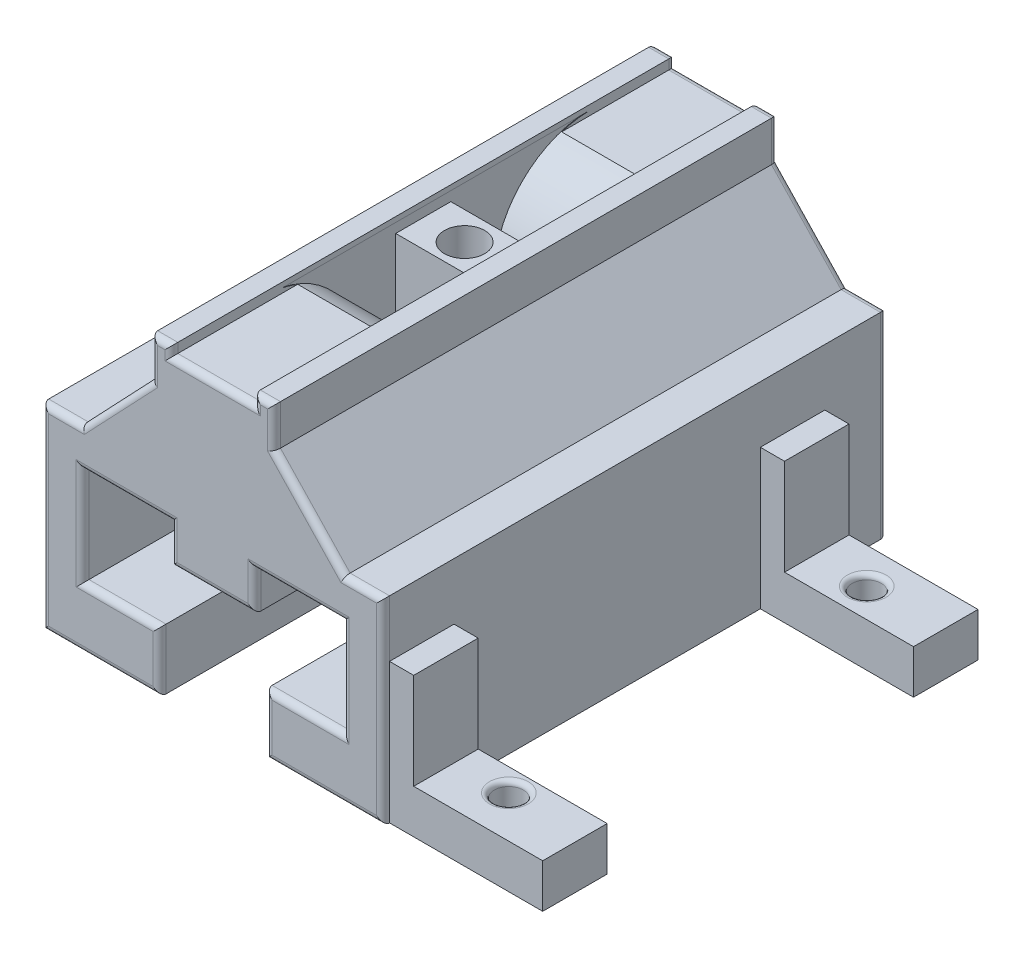
SolidWorks part; units mm, degrees
ref_plane "Front" through (0, 0, 0) normal (0, 0, 1) x (1, 0, 0)
ref_plane "Top" through (0, 0, 0) normal (0, 1, 0) x (1, 0, 0)
ref_plane "Right" through (0, 0, 0) normal (1, 0, 0) x (0, 0, -1)
sketch "Sketch2" plane through (0, 0, 0) normal (0, 0, 1) x (1, 0, 0)
  line L0 (-4.175, 2.6476) -> (-10.25, 2.6476)
  line L1 (-10.25, 2.6476) -> (-10.25, 10.3311)
  line L2 (-10.25, 10.3311) -> (-3.3, 10.3311)
  line L3 (-3.3, 10.3311) -> (-3.3, 7.2831)
  line L4 (-3.3, 7.2831) -> (3.3, 7.2831)
  line L5 (0, -13.7255) -> (0, 13.7255) construction
  line L6 (-4.175, 2.6476) -> (-4.175, -2.1149)
  line L7 (-4.175, -2.1149) -> (-13.425, -2.1149)
  line L8 (-13.425, -2.1149) -> (-13.425, 13.3791)
  line L9 (-13.425, 13.3791) -> (-10.325, 13.3791)
  line L10 (-10.325, 13.3791) -> (-4.8375, 19.1576)
  line L11 (-4.8375, 19.1576) -> (-4.8375, 22.3326)
  line L12 (-4.8375, 22.3326) -> (-3.25, 22.3326)
  line L13 (-3.25, 22.3326) -> (-3.25, 21.5706)
  line L14 (-3.25, 21.5706) -> (3.25, 21.5706)
  line L15 (3.25, 22.3326) -> (3.25, 21.5706)
  line L16 (4.8375, 22.3326) -> (3.25, 22.3326)
  line L17 (4.8375, 19.1576) -> (4.8375, 22.3326)
  line L18 (10.325, 13.3791) -> (4.8375, 19.1576)
  line L19 (13.425, 13.3791) -> (10.325, 13.3791)
  line L20 (13.425, -2.1149) -> (13.425, 13.3791)
  line L21 (4.175, -2.1149) -> (13.425, -2.1149)
  line L22 (4.175, 2.6476) -> (4.175, -2.1149)
  line L23 (3.3, 10.3311) -> (3.3, 7.2831)
  line L24 (10.25, 10.3311) -> (3.3, 10.3311)
  line L25 (10.25, 2.6476) -> (10.25, 10.3311)
  line L26 (4.175, 2.6476) -> (10.25, 2.6476)
  point P23 (0, 21.5706)
  point P32 (0, 7.2831)
  dimension "D1" = 4.7625
  dimension "D2" = 9.25
  dimension "D3" = 3.175
  dimension "D4" = 15.494
  dimension "D5" = 3.048
  dimension "D6" = 3.048
  dimension "D7" = 14.2875
  dimension "D8" = 3.175
  dimension "D9" = 0.762
  dimension "D10" = 1.5875
  dimension "D11" = 3.25
  dimension "D12" = 3.1
  dimension "D13" = 6.95
  dimension "D14" = 3.3
extrude "Boss-Extrude1" add sketch "Sketch2" along normal blind 39.6875
sketch "Sketch3" plane through (0, 21.5706, 0) normal (0, 1, 0) x (1, 0, 0)
  line L0 (0, 0) -> (0, -39.6875) construction
  line L1 (-13.425, -19.8438) -> (13.425, -19.8438) construction
  line L2 (-13.425, -39.6875) -> (-13.425, 0) construction
  line L3 (13.425, -39.6875) -> (13.425, 0) construction
  line L4 (3.25, 0) -> (-3.25, 0)
  line L5 (-3.25, 0) -> (-3.25, -39.6875)
  line L6 (-3.25, -39.6875) -> (3.25, -39.6875)
  line L7 (3.25, -39.6875) -> (3.25, 0)
  line L8 (3.25, 0) -> (-3.25, 0)
  line L9 (-3.25, 0) -> (-3.25, -39.6875)
  line L10 (-3.25, -39.6875) -> (3.25, -39.6875)
  line L11 (3.25, -39.6875) -> (3.25, 0)
  circle A0 centre (0, -19.8437) radius 1.5875
  dimension "D2" = 3.175
  dimension "D1" = 0
extrude "Cut-Extrude1" cut sketch "Sketch3" against normal blind 39.6875 contours A0 region at (0, 21.5706, 19.8437)
sketch "Sketch4" plane through (0, 7.2831, 0) normal (0, -1, 0) x (1, 0, 0)
  line L1 (1.5935, 17.0837) -> (3.187, 19.8437)
  line L2 (3.187, 19.8437) -> (1.5935, 22.6037)
  line L3 (1.5935, 22.6037) -> (-1.5935, 22.6037)
  line L4 (-3.3, 0) -> (3.3, 0)
  line L5 (3.3, 0) -> (3.3, 39.6875)
  line L6 (3.3, 39.6875) -> (-3.3, 39.6875)
  line L7 (-3.3, 39.6875) -> (-3.3, 0)
  line L8 (-3.3, 0) -> (3.3, 0)
  line L9 (3.3, 0) -> (3.3, 39.6875)
  line L10 (3.3, 39.6875) -> (-3.3, 39.6875)
  line L11 (-3.3, 39.6875) -> (-3.3, 0)
  line L12 (-1.5935, 22.6037) -> (-3.187, 19.8437)
  line L13 (-3.187, 19.8437) -> (-1.5935, 17.0837)
  line L14 (-1.5935, 17.0837) -> (1.5935, 17.0837)
  circle A0 centre (0, 19.8437) radius 2.76 construction
  circle M11 centre (0, 19.8437) radius 1.5875
  dimension "D2" = 5.52
  dimension "D1" = 0
extrude "Cut-Extrude3" cut sketch "Sketch4" against normal blind 5 contours M11 | L12 L13 M11 | L13 L14 M11 | L14 L1 M11 | L1 L2 M11 | L2 L3 M11 | L3 L12 M11 region at (0, 7.2831, 17.1681) region at (0, 7.2831, 19.8437)
sketch "Sketch5" plane through (-3.3, 0, 0) normal (-1, 0, 0) x (0, 0, 1)
  line L6 (30.9355, 21.9296) -> (6.7938, 21.9296)
  line L12 (9.474, 7.2831) -> (17.626, 7.2831)
  line L18 (21.9668, 7.2831) -> (30.1189, 7.2831)
  line L19 (21.9668, 21.1284) -> (17.626, 21.1284)
  line L20 (21.9668, 7.2831) -> (21.9668, 21.1284)
  line L21 (17.626, 21.1284) -> (17.626, 7.2831)
  arc A0 (30.9355, 21.9296) -> (30.1189, 7.2831) centre (32.5149, 14.4955) ccw
  arc A1 (6.7938, 21.9296) -> (9.474, 7.2831) centre (6.631, 14.3314) cw
  point P0 (17.626, 7.2831)
  point P1 (7.0661, 21.9189)
  point P3 (17.7745, 21.8404)
  point P6 (18.9107, 22.0728)
  dimension "D2" = 4.3408
  dimension "D3" = 7.6
  dimension "D1" = 7.6
  dimension "D4" = 13.8453
  dimension "D5" = 0.8012
  dimension "D6" = 8.1521
extrude "Cut-Extrude5" cut sketch "Sketch5" against normal blind 6.5
sketch "Sketch6" plane through (-3.25, 0, 0) normal (1, 0, 0) x (0, 0, -1)
  line L0 (-26.3863, 10.5206) -> (-13.2066, 10.5206)
  line L1 (-9.474, 7.2831) -> (-30.1189, 7.2831)
fillet "Fillet1" radius 0.508 52 edges at (-7.2125, 2.6476, 0) (-10.25, 6.4894, 0) (6.775, 10.3311, 0) (-3.3, 8.8071, 0) (0, 7.2831, 0) (3.3, 8.8071, 0) (10.25, 6.4894, 0) (7.2125, 2.6476, 0) (4.175, 0.2664, 0) (8.8, -2.1149, 0) (13.425, 5.6321, 0) (11.875, 13.3791, 0) (7.5812, 16.2684, 0) (4.8375, 20.7451, 0) (4.0437, 22.3326, 0) (3.25, 21.9516, 0) (0, 21.5706, 0) (-3.25, 21.9516, 0) (-4.0437, 22.3326, 0) (-4.8375, 20.7451, 0) (-7.5812, 16.2684, 0) (-11.875, 13.3791, 0) (-13.425, 5.6321, 0) (-8.8, -2.1149, 0) (-4.175, 0.2664, 0) (-8.8, -2.1149, 39.6875) (-13.425, 5.6321, 39.6875) (-11.875, 13.3791, 39.6875) (-7.5812, 16.2684, 39.6875) (-4.8375, 20.7451, 39.6875) (-4.0437, 22.3326, 39.6875) (-3.25, 21.9516, 39.6875) (0, 21.5706, 39.6875) (3.25, 21.9516, 39.6875) (4.0437, 22.3326, 39.6875) (4.8375, 20.7451, 39.6875) (7.5812, 16.2684, 39.6875) (11.875, 13.3791, 39.6875) (13.425, 5.6321, 39.6875) (8.8, -2.1149, 39.6875) (4.175, 0.2664, 39.6875) (7.2125, 2.6476, 39.6875) (10.25, 6.4894, 39.6875) (6.775, 10.3311, 39.6875) (3.3, 8.8071, 39.6875) (0, 7.2831, 39.6875) (-3.3, 8.8071, 39.6875) (-10.25, 6.4894, 39.6875) (-7.2125, 2.6476, 39.6875) (-4.175, 0.2664, 39.6875) (-6.775, 10.3311, 0) (-6.775, 10.3311, 39.6875)
sketch "Sketch7" plane through (13.425, 0, 0) normal (1, 0, 0) x (0, 0, -1)
  line L0 (-39.1795, -2.1149) -> (-0.508, -2.1149) construction
  line L1 (-39.1795, -2.1149) -> (-34.0995, -2.1149)
  line L2 (-39.1795, -2.1149) -> (-39.1795, 8.9054)
  line L3 (-39.1795, 8.9054) -> (-34.0995, 8.9054)
  line L4 (-34.0995, -2.1149) -> (-34.0995, 8.9054)
  line L5 (-9.9695, -2.1149) -> (-4.8895, -2.1149)
  line L6 (-9.9695, -2.1149) -> (-9.9695, 8.9054)
  line L7 (-9.9695, 8.9054) -> (-4.8895, 8.9054)
  line L8 (-4.8895, -2.1149) -> (-4.8895, 8.9054)
  dimension "D1" = 5.08
  dimension "D2" = 24.13
extrude "Boss-Extrude2" add sketch "Sketch7" along normal blind 1.905
sketch "Sketch8" plane through (15.33, 0, 0) normal (1, 0, 0) x (0, 0, -1)
  line L0 (-39.1795, 1.336) -> (-34.0995, 1.336)
  line L1 (-9.9695, 1.336) -> (-4.8895, 1.336)
  line L4 (-39.1795, 8.9054) -> (-39.1795, -2.1149)
  line L5 (-39.1795, -2.1149) -> (-34.0995, -2.1149)
  line L6 (-34.0995, -2.1149) -> (-34.0995, 8.9054)
  line L7 (-34.0995, 8.9054) -> (-39.1795, 8.9054)
  line L8 (-39.1795, 8.9054) -> (-39.1795, -2.1149)
  line L9 (-39.1795, -2.1149) -> (-34.0995, -2.1149)
  line L10 (-34.0995, -2.1149) -> (-34.0995, 8.9054)
  line L11 (-34.0995, 8.9054) -> (-39.1795, 8.9054)
  line L12 (-9.9695, 8.9054) -> (-9.9695, -2.1149)
  line L13 (-9.9695, -2.1149) -> (-4.8895, -2.1149)
  line L14 (-4.8895, -2.1149) -> (-4.8895, 8.9054)
  line L15 (-4.8895, 8.9054) -> (-9.9695, 8.9054)
  line L16 (-9.9695, 8.9054) -> (-9.9695, -2.1149)
  line L17 (-9.9695, -2.1149) -> (-4.8895, -2.1149)
  line L18 (-4.8895, -2.1149) -> (-4.8895, 8.9054)
  line L19 (-4.8895, 8.9054) -> (-9.9695, 8.9054)
  line M9 (-39.1795, 8.9054) -> (-39.1795, -2.1149)
  line M10 (-39.1795, -2.1149) -> (-34.0995, -2.1149)
  line M11 (-34.0995, -2.1149) -> (-34.0995, 8.9054)
  dimension "D1" = 0
  dimension "D2" = 0
extrude "Boss-Extrude3" add sketch "Sketch8" along normal blind 10.16 contours L0 M9 M10 M11 | L17 L18 L1 L16 region at (15.33, -0.3894, 36.6395) region at (15.33, -0.3894, 7.4295)
sketch "Sketch9" plane through (0, -2.1149, 0) normal (0, -1, 0) x (1, 0, 0)
  line L11 (4.175, 39.1795) -> (4.175, 0.508)
  line L12 (4.175, 0.508) -> (13.425, 0.508)
  line L13 (13.425, 0.508) -> (13.425, 4.8895)
  line L14 (13.425, 4.8895) -> (25.49, 4.8895)
  line L15 (25.49, 4.8895) -> (25.49, 9.9695)
  line L16 (25.49, 9.9695) -> (13.425, 9.9695)
  line L17 (13.425, 9.9695) -> (13.425, 34.0995)
  line L18 (13.425, 34.0995) -> (25.49, 34.0995)
  line L19 (25.49, 34.0995) -> (25.49, 39.1795)
  line L20 (25.49, 39.1795) -> (13.425, 39.1795)
  line L21 (13.425, 39.1795) -> (4.175, 39.1795)
  line L22 (4.175, 39.1795) -> (4.175, 0.508)
  line L23 (4.175, 0.508) -> (13.425, 0.508)
  line L24 (13.425, 0.508) -> (13.425, 4.8895)
  line L25 (13.425, 4.8895) -> (25.49, 4.8895)
  line L26 (25.49, 4.8895) -> (25.49, 9.9695)
  line L27 (25.49, 9.9695) -> (13.425, 9.9695)
  line L28 (13.425, 9.9695) -> (13.425, 34.0995)
  line L29 (13.425, 34.0995) -> (25.49, 34.0995)
  line L30 (25.49, 34.0995) -> (25.49, 39.1795)
  line L31 (25.49, 39.1795) -> (13.425, 39.1795)
  line L32 (13.425, 39.1795) -> (4.175, 39.1795)
  circle A0 centre (19.521, 7.6835) radius 1.143
  circle A1 centre (19.521, 35.8775) radius 1.143
  dimension "D2" = 2.286
  dimension "D4" = 2.286
  dimension "D6" = 6.096
  dimension "D7" = 6.096
  dimension "D3" = 2.286
  dimension "D5" = 1.778
  dimension "D1" = 0
extrude "Cut-Extrude7" cut sketch "Sketch9" against normal up to next contours A1 | A0 region at (19.521, -2.1149, 7.6835) region at (19.521, -2.1149, 35.8775)
fillet "Fillet2" radius 0.381 4 edges at (20.664, -2.1149, 7.6835) (20.664, -2.1149, 35.8775) (18.378, 1.336, 7.6835) (18.378, 1.336, 35.8775)
